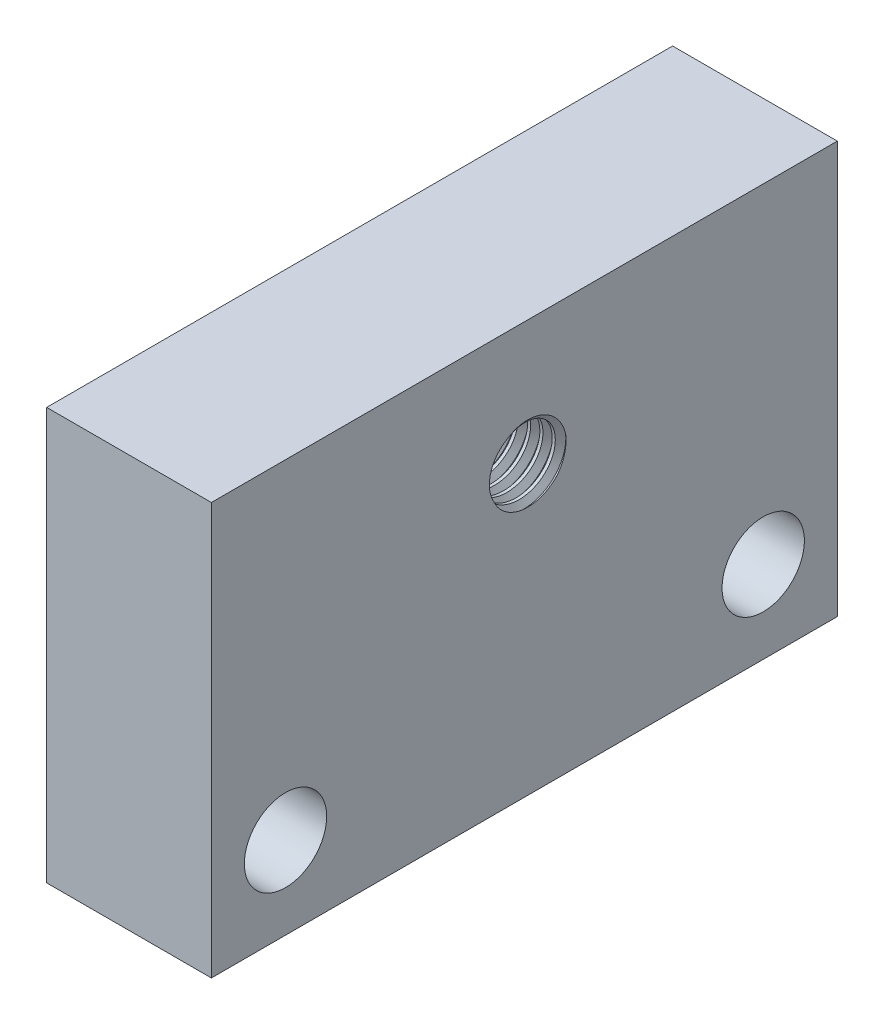
SolidWorks part; units mm, degrees
ref_plane "Front Plane" through (0, 0, 0) normal (0, 0, 1) x (1, 0, 0)
ref_plane "Top Plane" through (0, 0, 0) normal (0, 1, 0) x (1, 0, 0)
ref_plane "Right Plane" through (0, 0, 0) normal (1, 0, 0) x (0, 0, -1)
sketch "Sketch1" plane through (0, 0, 0) normal (0, 1, 0) x (1, 0, 0)
  line L1 (10, 38) -> (-10, 38)
  line L2 (10, 38) -> (10, -38)
  line L3 (10, -38) -> (-10, -38)
  line L4 (-10, 38) -> (-10, -38)
  line L5 (10, 38) -> (-10, -38) construction
  line L6 (10, -38) -> (-10, 38) construction
  point P0 (0, 0)
  dimension "D1" = 20
  dimension "D2" = 76
extrude "Boss-Extrude1" add sketch "Sketch1" along normal blind 50
sketch "Sketch2" plane through (10, 0, 0) normal (1, 0, 0) x (0, 0, -1)
  line L0 (0, 41.9858) -> (0, -3.6541) construction
  line L1 (-38, 0) -> (38, 0) construction
  circle A0 centre (-29, 10) radius 5
  circle A1 centre (29, 10) radius 5
  dimension "D1" = 10
  dimension "D2" = 10
  dimension "D3" = 58
hole_wizard "M10 Tapped Hole1" positions "Sketch5" profile "Sketch6" tap size "M10" standard "ISO" end condition through all
sketch "Sketch5" plane through (10, 0, 0) normal (1, 0, 0) x (0, 0, -1)
  line L0 (0, 41.9858) -> (0, -3.6541) construction
  point P0 (0, 35)
  point P4 (0, 34.2391)
  dimension "D1" = 35
sketch "Sketch6" plane through (10, 35, 0) normal (0, 1, 0) x (0, 0, -1)
  line L0 (0, 0) -> (0, 20)
  line L1 (0, 20) -> (4.25, 20)
  line L2 (4.25, 20) -> (4.25, 0)
  line L5 (4.25, 0) -> (0, 0)
  line L11 (0, -6.35) -> (0, 107.95) construction
  dimension "Thru Tap Drill Dia." = 8.5
  dimension "Thru Tap Drill Depth" = 20
cosmetic thread "Hole Thread1" parameters "D2"=10
thread "Thread1" pitch 1.5 method cut profile "Thread Profile1" start angle 0, offset 0, length 20, pitch 1.5, diameter 8.5
ref_plane "Plane1" through (-10, 35, -4.25) normal (0, -1, 0) x (0, 0, -1)
sketch "Thread Profile1" plane through (-10, 35, -4.25) normal (0, -1, 0) x (0, 0, -1)
  line L0 (0, 0) -> (0, 1.5) construction
  line L1 (0, 0) -> (0.8119, 0.4687)
  line L2 (0.8119, 0.4687) -> (0.8119, 0.6562)
  line L3 (0.8119, 0.6562) -> (0, 1.125)
  line L4 (0.8119, 0.5625) -> (0, 0.5625) construction
  line L11 (0, 0) -> (0, 1.125)
  point P2 (0, 0)
  dimension "Pitch" = 1.5
  dimension "Profile_Angle" = 60
  dimension "Profile_Land" = 0.1875
  dimension "Profile_Height" = 0.8119
extrude "Cut-Extrude2" cut sketch "Sketch2" against normal through all
